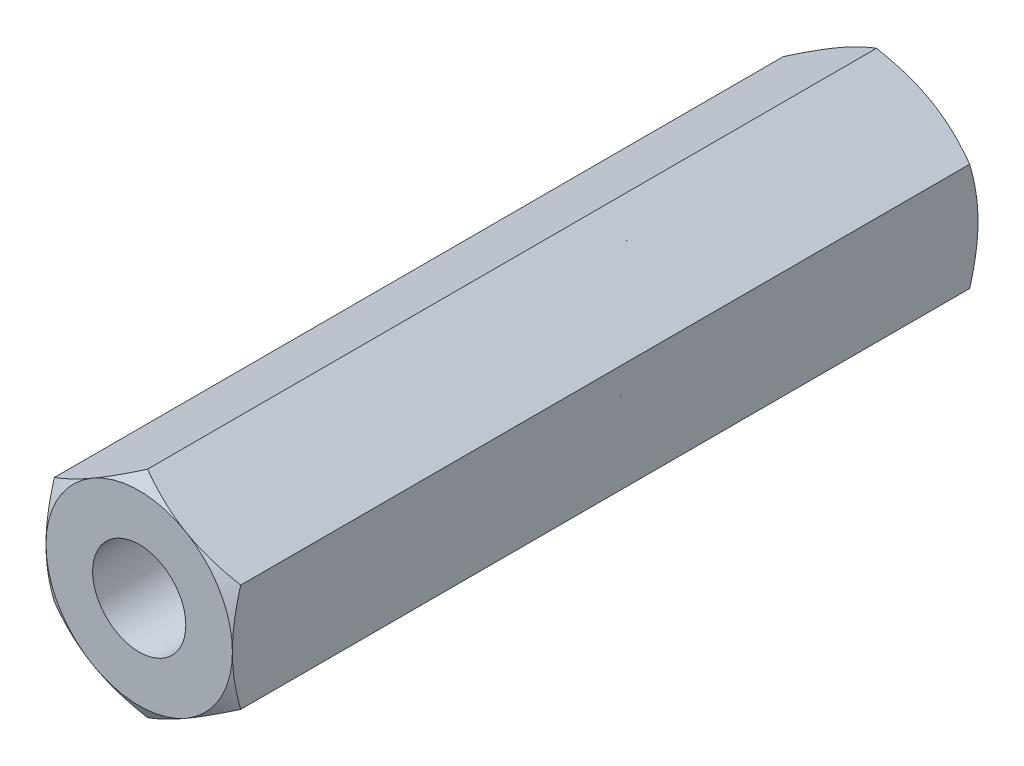
SolidWorks part; units mm, degrees
ref_plane "Front Plane" through (0, 0, 0) normal (0, 0, 1) x (1, 0, 0)
ref_plane "Top Plane" through (0, 0, 0) normal (0, 1, 0) x (1, 0, 0)
ref_plane "Right Plane" through (0, 0, 0) normal (1, 0, 0) x (0, 0, -1)
sketch "Sketch3" plane through (0, 0, 0) normal (1, 0, 0) x (0, 0, -1)
  line L0 (-20, 0) -> (20, 0) construction
  line L1 (0, 5) -> (0, -5) construction
  line L2 (-20, 2.5) -> (-20, -2.5) construction
  line L3 (20, -2.5) -> (20, 2.5) construction
  point P2 (7.3, 0)
  point P3 (-7.3, 0)
  dimension "Length" = 40
  dimension "Min Thread Length" = 12.7
  dimension "D1" = 12.7
  dimension "Thread Dia" = 5
  dimension "Hex" = 10
sketch "Sketch1" plane through (0, 0, 0) normal (0, 0, 1) x (1, 0, 0)
  line L1 (0, 5.7735) -> (-5, 2.8868)
  line L2 (-5, 2.8868) -> (-5, -2.8868)
  line L3 (-5, -2.8868) -> (0, -5.7735)
  line L4 (0, -5.7735) -> (5, -2.8868)
  line L5 (5, -2.8868) -> (5, 2.8868)
  line L6 (5, 2.8868) -> (0, 5.7735)
  circle A0 centre (0, 0) radius 5 construction
  circle A1 centre (0, 0) radius 2.5
extrude "Extrude1" add sketch "Sketch1" along normal up to vertex (20 mm away) and the other way up to vertex (20 mm away) up to point (0, 0, 20) other way up to point (0, 0, -20)
sketch "Sketch11" plane through (0, 0, -20) normal (0, 0, -1) x (-1, 0, 0)
  circle A0 centre (0, 0) radius 2.5 construction
  circle A1 centre (0, 0) radius 2.5
curve "Helix/Spiral1" [suppressed] parameters "Pitch"=0.8
sketch "Sketch12" plane through (0, 0, 0) normal (1, 0, 0) x (0, 0, -1)
  line L0 (20.7, 2.5001) -> (20, 2.5001)
  line L1 (20.7, 2.5001) -> (20.4, 1.9805)
  line L2 (20.4, 1.9805) -> (20.3, 1.9805)
  line L3 (20.3, 1.9805) -> (20, 2.5001)
  line L4 (20.35, 1.9805) -> (20.35, 2.5001) construction
  line L5 (20.55, 2.2403) -> (20.15, 2.2403) construction
  line L6 (20, -2.8868) -> (20, 2.8868) construction
  line L7 (20, 2.5001) -> (20, 2.5) construction
  dimension "D1" = 0.1
  dimension "D2" = 0.4
  dimension "D3" = 60
  dimension "D4" = 0.0001
sweep "Sweep1" [suppressed] add profiles "Sketch12" path "Helix/Spiral1"
sketch "Sketch6" plane through (0, 0, -20) normal (0, 0, -1) x (-1, 0, 0)
  line L6 (0, 5.7735) -> (-5, 2.8868)
  line L7 (-5, 2.8868) -> (-5, -2.8868)
  line L8 (-5, -2.8868) -> (0, -5.7735)
  line L9 (0, -5.7735) -> (5, -2.8868)
  line L10 (5, -2.8868) -> (5, 2.8868)
  line L11 (5, 2.8868) -> (0, 5.7735)
  line L12 (0, 5.7735) -> (-5, 2.8868)
  line L13 (-5, 2.8868) -> (-5, -2.8868)
  line L14 (-5, -2.8868) -> (0, -5.7735)
  line L15 (0, -5.7735) -> (5, -2.8868)
  line L16 (5, -2.8868) -> (5, 2.8868)
  line L17 (5, 2.8868) -> (0, 5.7735)
  dimension "D1" = 0
extrude "Extrude2" [suppressed] cut sketch "Sketch6" along normal through all
sketch "Sketch7" plane through (0, 0, -20) normal (0, 0, -1) x (-1, 0, 0)
  circle A2 centre (0, 0) radius 2.5508
  circle A3 centre (0, 0) radius 2.5508
  dimension "D1" = 0.0508
extrude "Extrude3" cut sketch "Sketch7" against normal through all draft 43
sketch "Sketch8" plane through (0, 0, -20) normal (0, 0, -1) x (-1, 0, 0)
  circle A0 centre (0, 0) radius 5 construction
  circle A1 centre (0, 0) radius 5
extrude "Extrude4" cut sketch "Sketch8" against normal through all draft 60 flip side to cut
mirror "Mirror1" about plane through (0, 0, 0) normal (0, 0, 1) of "Extrude4", "Extrude2"
sketch "Sketch14" plane through (0, 0, 20) normal (0, 0, 1) x (1, 0, 0)
  circle A0 centre (0, 0) radius 2.5 construction
  circle A1 centre (0, 0) radius 2.5
extrude "Cut-Extrude1" [suppressed] cut sketch "Sketch14" against normal through all draft 45
sketch "Sketch9" plane through (0, 0, 0) normal (1, 0, 0) x (0, 0, -1)
  line L1 (-7.3, 2.0508) -> (7.3, 2.0508)
  line L2 (-7.3, 2.0508) -> (-7.3, 0)
  line L3 (-7.3, 0) -> (7.3, 0)
  line L4 (7.3, 2.0508) -> (7.3, 0)
  line L7 (-20, 0) -> (20, 0) construction
  dimension "D1" = 2.0508
revolve "Revolve" add sketch "Sketch9" angle 360 about L0
sketch "Sketch10" plane through (0, 0, 0) normal (1, 0, 0) x (0, 0, -1)
  line L0 (20, 2.5) -> (7.3, 2.5)
  line L1 (-20, 2.5) -> (-7.3, 2.5)
  line L2 (7.3, 2.5) -> (7.3, -2.5)
  line L3 (-12.5, -2.0508) -> (-7.3, -2.0508)
  line L4 (-7.3, 2.5) -> (-7.3, -2.0508)
  line L5 (7.3, -2.5) -> (20, -2.5)
  dimension "D1" = 4.5508
  dimension "D2" = 5.2
sketch "Sketch15" plane through (5, 0, 0) normal (1, 0, 0) x (0, 0, -1)
  line L0 (-20, 2.5) -> (-20, -2.5) construction
  line L1 (-20, 0) -> (20, 0) construction
  line L3 (20, -2.5) -> (20, 2.5) construction
  line L4 (-20, 2.5) -> (-20, -2.5)
  line L7 (20, -2.5) -> (20, 2.5)
  line L9 (-20, -2.5) -> (-7.3036, -2.5) construction
  line L11 (-20, 2.5) -> (-7.3036, 2.5) construction
  line L12 (-7.3036, -2.5) -> (-7.3036, 2.5) construction
  line L13 (7.2978, -2.5) -> (20, -2.5) construction
  line L14 (7.2978, -2.5) -> (7.2978, 2.5) construction
  line L15 (7.2978, 2.5) -> (20, 2.5) construction
  point P0 (7.3, 0)
  point P2 (-7.3, 0)
  point P20 (-7.3036, 0)
  point P21 (7.2978, 0)
  point P22 (7.2978, 0)
  dimension "D1" = 12.7022
  dimension "D2" = 12.6964
equation "\"D1@Sketch3\" = \"Min Thread Length@Sketch3\""
equation "\"D3@Helix/Spiral1\" = \"Length@Sketch3\"+\"Pitch@Helix/Spiral1\""
equation "\"D1@Sketch12\" = \"Pitch@Helix/Spiral1\"*.125"
equation "\"D2@Sketch12\" = \"Pitch@Helix/Spiral1\"*.5"
